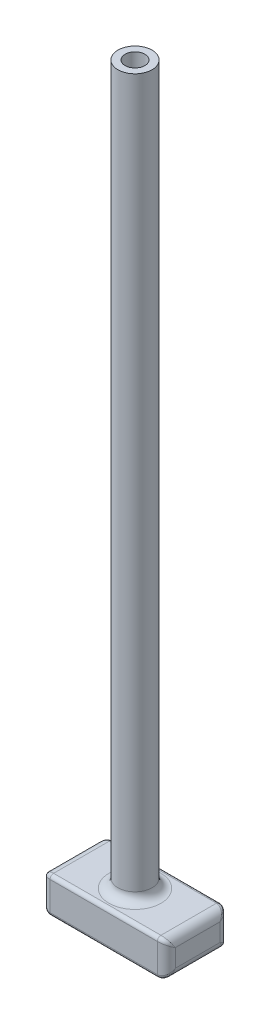
SolidWorks part; units mm, degrees
material "3003 Alloy"
ref_plane "Front Plane" through (0, 0, 0) normal (0, 0, 1) x (1, 0, 0)
ref_plane "Top Plane" through (0, 0, 0) normal (0, 1, 0) x (1, 0, 0)
ref_plane "Right Plane" through (0, 0, 0) normal (1, 0, 0) x (0, 0, -1)
sketch "Sketch1" plane through (0, 0, 0) normal (0, 1, 0) x (1, 0, 0)
  circle A0 centre (0, 0) radius 9.525
  circle A1 centre (0, 0) radius 5.525
  dimension "D1" = 19.05
  dimension "D2" = 11.05
extrude "Boss-Extrude1" add sketch "Sketch1" along normal blind 400 and the other way blind 21
sketch "Sketch2" plane through (0, -21, 0) normal (0, -1, 0) x (1, 0, 0)
  line L1 (-35, -17.5) -> (35, -17.5)
  line L2 (-35, -17.5) -> (-35, 17.5)
  line L3 (-35, 17.5) -> (35, 17.5)
  line L4 (35, -17.5) -> (35, 17.5)
  line L5 (-35, -17.5) -> (35, 17.5) construction
  line L6 (-35, 17.5) -> (35, -17.5) construction
  point P0 (0, 0)
  dimension "D1" = 70
  dimension "D2" = 35
extrude "Boss-Extrude2" add sketch "Sketch2" against normal blind 20
sketch "Sketch4" plane through (0, -1, 0) normal (0, 1, 0) x (1, 0, 0)
  circle A0 centre (0, 0) radius 5.525
  circle A1 centre (0, 0) radius 9.525
extrude "Cut-Extrude1" cut sketch "Sketch4" against normal blind 20 draft 12 contours A0 region at (0, -1, 0)
fillet "Fillet1" radius 5 9 edges at (-35, -11, -17.5) (-35, -1, 0) (-35, -11, 17.5) (-35, -21, 0) (35, -11, 17.5) (35, -1, 0) (35, -11, -17.5) (35, -21, 0) (0, -1, 9.525)
fillet "Fillet2" radius 2 12 edges at (33.5355, -19.5355, 16.0355) (-33.5355, -19.5355, 16.0355) (-33.5355, -19.5355, -16.0355) (33.5355, -19.5355, -16.0355) (33.5355, -2.4645, 16.0355) (-33.5355, -2.4645, 16.0355) (-33.5355, -2.4645, -16.0355) (33.5355, -2.4645, -16.0355) (0, -21, 17.5) (0, -21, -17.5) (0, -1, 17.5) (0, -1, -17.5)
